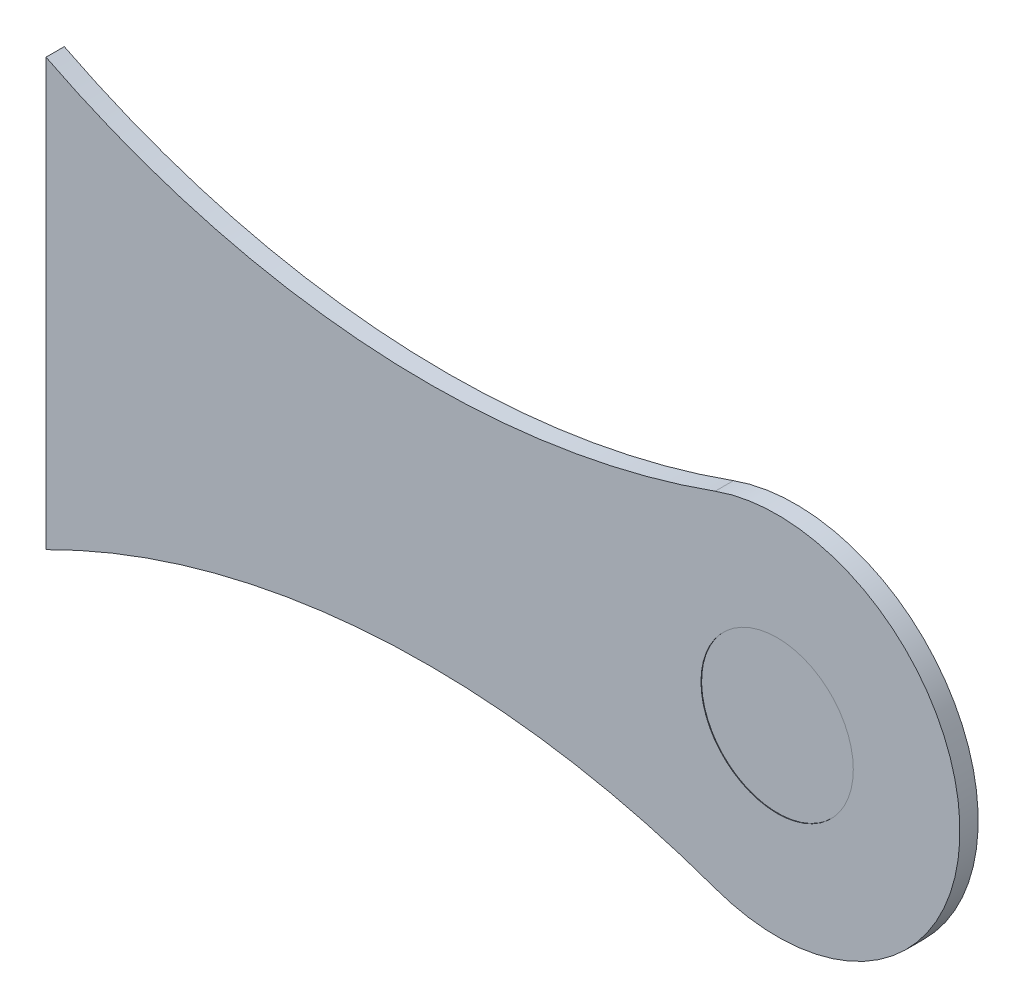
SolidWorks part; units mm, degrees
material "Custom Plastic"
ref_plane "Front Plane" through (0, 0, 0) normal (0, 0, 1) x (1, 0, 0)
ref_plane "Top Plane" through (0, 0, 0) normal (0, 1, 0) x (1, 0, 0)
ref_plane "Right Plane" through (0, 0, 0) normal (1, 0, 0) x (0, 0, -1)
sketch "Sketch1" plane through (0, 0, 0) normal (0, 1, 0) x (1, 0, 0)
  line L0 (0, 0) -> (-120, 0) construction
  line L1 (-120, 35) -> (-120, -35)
  line L2 (-57.2373, 20) -> (-120, 20) construction
  circle A0 centre (0, 0) radius 12.5
  arc A1 (-10.1722, 28.2228) -> (-10.1722, -28.2228) centre (0, 0) cw
  arc A2 (-10.1722, 28.2228) -> (-120, 35) centre (-57.2373, 158.8053) cw
  arc A3 (-10.1722, -28.2228) -> (-120, -35) centre (-57.2373, -158.8053) ccw
  point P13 (-120, 0)
  dimension "D1" = 25
  dimension "D2" = 30
  dimension "D3" = 20
  dimension "D4" = 120
  dimension "D5" = 70
  dimension "D6" = 150
extrude "Boss-Extrude1" add sketch "Sketch1" along normal mid plane 3
extrude "Boss-Extrude2" add sketch "Sketch1<3>" along normal offset from surface 0.1 and the other way offset from surface 0.1 contours A0 region at (0, 0, 0) up to face at (-55.3932, 1.5, 0) other way up to face at (-55.3932, -1.5, 0)
sketch "Sketch1<3>" plane through (0, 0, 0) normal (0, 1, 0) x (1, 0, 0) same geometry as "Sketch1"
move or copy body "Body-Move/Copy1" bodies to move or copy 102 copy no rotation origin (0, 0, 0) rotation axis (1, 0, 0) rotation angle 90
